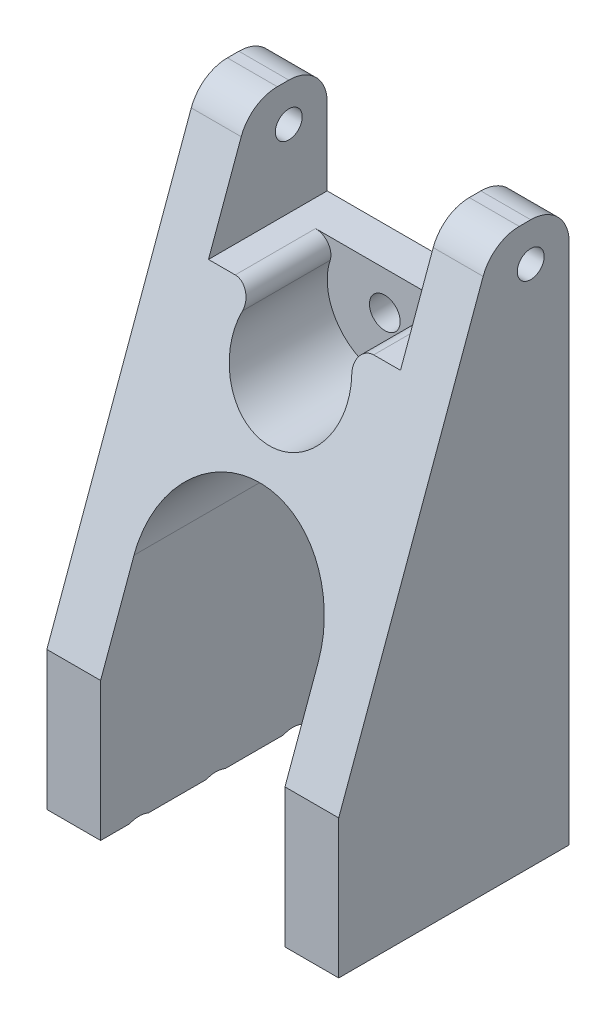
SolidWorks part; units mm, degrees
ref_plane "Front Plane" through (0, 0, 0) normal (0, 0, 1) x (1, 0, 0)
ref_plane "Top Plane" through (0, 0, 0) normal (0, 1, 0) x (1, 0, 0)
ref_plane "Right Plane" through (0, 0, 0) normal (1, 0, 0) x (0, 0, -1)
sketch "Sketch1" plane through (0, 0, 0) normal (0, 0, 1) x (1, 0, 0)
  line L0 (-12, 0) -> (-12, -30)
  line L1 (-12, -30) -> (12, -30) construction
  line L2 (12, -30) -> (12, 0)
  line L4 (-19, -30) -> (-12, -30)
  line L5 (12, -30) -> (19, -30)
  line L11 (-19, -30) -> (-19, 43)
  line L12 (-19, 43) -> (19, 43)
  line L13 (19, 43) -> (19, -30)
  arc A0 (12, 0) -> (-12, 0) centre (0, 0) ccw
  dimension "D1" = 24
  dimension "D2" = 38
  dimension "D3" = 73
  dimension "D4" = 30
extrude "Boss-Extrude1" add sketch "Sketch1" along normal blind 30
sketch "Sketch2" plane through (0, -30, 0) normal (0, -1, 0) x (1, 0, 0)
  line L0 (-15, 5) -> (15, 5) construction
  line L1 (0, 0) -> (0, 5) construction
  circle A0 centre (-15, 5) radius 2.25
  circle A1 centre (15, 5) radius 2.25
  circle A4 centre (-15, 15) radius 2.25
  circle A5 centre (15, 15) radius 2.25
  circle A6 centre (-15, 25) radius 2.25
  circle A7 centre (15, 25) radius 2.25
  dimension "D1" = 4.5
  dimension "D2" = 30
  dimension "D3" = 5
  dimension "D4" = 3
extrude "Cut-Extrude1" cut sketch "Sketch2" against normal blind 15
fillet "Fillet1" radius 5 1 edges at (0, 43, 0)
chamfer "Chamfer1" distance 20 angle 70 1 edges at (0, 43, 30) first distance on face at (0, 43, 17.5)
sketch "Sketch3" plane through (0, 43, 0) normal (0, 1, 0) x (1, 0, 0)
  line L1 (-12.5, 19.7985) -> (12.5, 19.7985)
  line L2 (-12.5, 19.7985) -> (-12.5, -19.7985)
  line L3 (-12.5, -19.7985) -> (12.5, -19.7985)
  line L4 (12.5, 19.7985) -> (12.5, -19.7985)
  line L5 (-12.5, 19.7985) -> (12.5, -19.7985) construction
  line L6 (-12.5, -19.7985) -> (12.5, 19.7985) construction
  point P0 (0, 0)
  dimension "D1" = 25
extrude "Cut-Extrude2" cut sketch "Sketch3" against normal blind 15
sketch "Sketch4" plane through (-19, 0, 0) normal (-1, 0, 0) x (0, 0, 1)
  circle A1 centre (5, 38) radius 1.75
  dimension "D1" = 3.5
extrude "Cut-Extrude3" cut sketch "Sketch4" against normal through all
chamfer "Chamfer2" distance 1 angle 45 6 edges at (-15, -30, 2.75) (15, -30, 2.75) (15, -30, 12.75) (15, -30, 22.75) (-15, -30, 12.75) (-15, -30, 22.75)
sketch "Sketch5" plane through (0, 0, 0) normal (0, 0, -1) x (-1, 0, 0)
  line L0 (0, 23) -> (0, 0) construction
  circle A0 centre (0, 23) radius 2
  dimension "D2" = 4
  dimension "D1" = 23
extrude "Cut-Extrude4" cut sketch "Sketch5" against normal through all
sketch "Sketch6" plane through (0, 0, 30) normal (0, 0, 1) x (1, 0, 0)
  circle A0 centre (0, 23) radius 7.5
  dimension "D1" = 15
extrude "Cut-Extrude5" cut sketch "Sketch6" against normal blind 25
fillet "Fillet2" radius 2 2 edges at (5.5902, 28, 10.2298) (-5.5902, 28, 10.2298)
fillet "Fillet3" radius 5 2 edges at (-15.75, 43, 10) (15.75, 43, 10)
